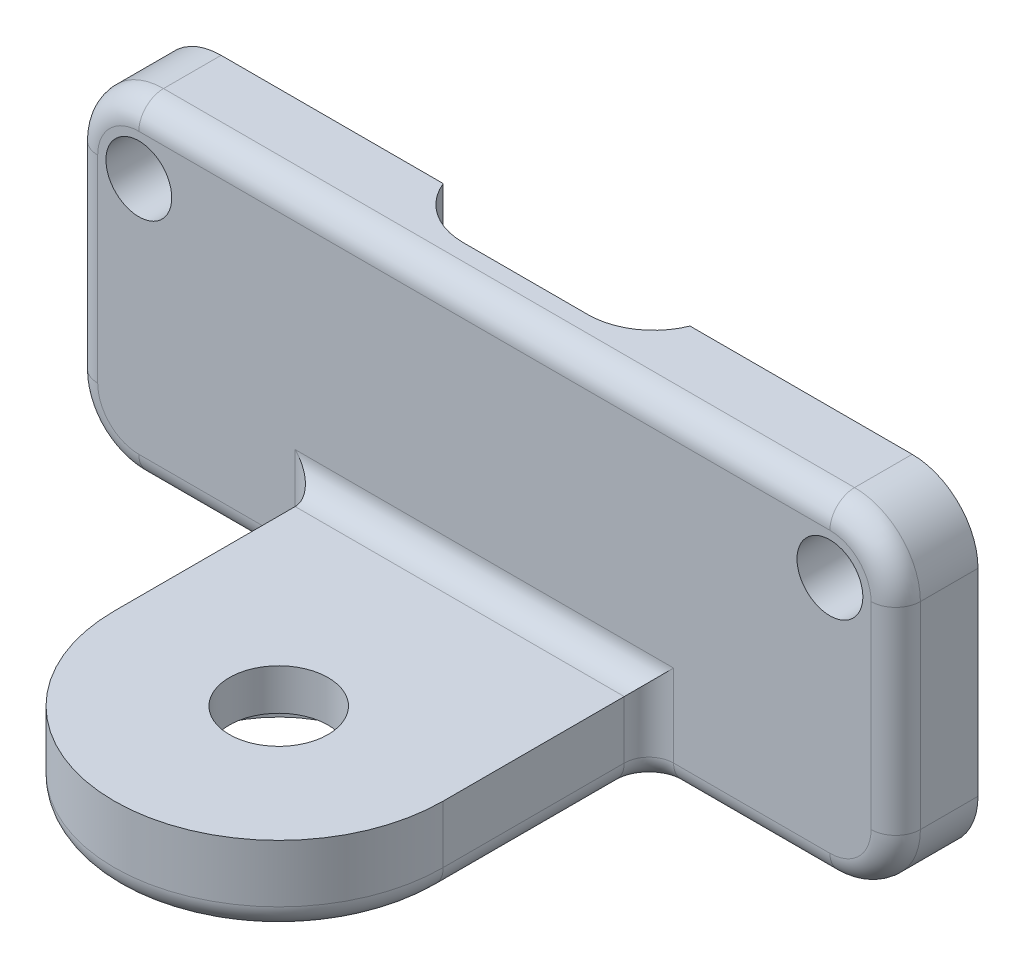
SolidWorks part; units mm, degrees
ref_plane "Спереди" through (0, 0, 0) normal (0, 0, 1) x (1, 0, 0)
ref_plane "Сверху" through (0, 0, 0) normal (0, 1, 0) x (1, 0, 0)
ref_plane "Справа" through (0, 0, 0) normal (1, 0, 0) x (0, 0, -1)
sketch "Эскиз1" plane through (0, 0, 0) normal (0, 0, 1) x (1, 0, 0)
  line L1 (50, -20) -> (-50, -20)
  line L2 (50, -20) -> (50, 20)
  line L3 (50, 20) -> (-50, 20)
  line L4 (-50, -20) -> (-50, 20)
  line L5 (50, -20) -> (-50, 20) construction
  line L6 (50, 20) -> (-50, -20) construction
  point P0 (0, 0)
  dimension "D1" = 100
  dimension "D2" = 40
extrude "Бобышка-Вытянуть1" add sketch "Эскиз1" along normal blind 10
sketch "Эскиз2" plane through (0, -20, 0) normal (0, -1, 0) x (1, 0, 0)
  line L0 (-20, 0) -> (-20, 35)
  line L1 (-50, 0) -> (50, 0) construction
  line L2 (-20, 0) -> (20, 0)
  line L3 (20, 0) -> (20, 35)
  line L4 (-50, 10) -> (-50, 0) construction
  arc A1 (-20, 35) -> (20, 35) centre (0, 35) cw
  point P4 (-19.4704, 35)
  dimension "D2" = 35
  dimension "D1" = 20
  dimension "D3" = 50
extrude "Бобышка-Вытянуть2" add sketch "Эскиз2" against normal blind 10 contours A1 L3 L2 L0
sketch "Эскиз4" plane through (0, -20, 0) normal (0, -1, 0) x (1, 0, 0)
  line L0 (-50, 0) -> (50, 0) construction
  line L1 (-50, 10) -> (-50, 0) construction
  circle A0 centre (0, 35) radius 12.5
  point P4 (0, 0)
  dimension "D1" = 25
  dimension "D3" = 50
  dimension "D2" = 35
extrude "Вырез-Вытянуть1" cut sketch "Эскиз4" against normal blind 5 contours A0
sketch "Эскиз5" plane through (0, -15, 0) normal (0, -1, 0) x (1, 0, 0)
  line L0 (-50, 10) -> (-50, 0) construction
  line L1 (-50, 0) -> (50, 0) construction
  circle A0 centre (0, 35) radius 6
  point P6 (24.3464, 47.591)
  point P9 (-32.7059, 65.9829)
  dimension "D1" = 12
  dimension "D2" = 50
  dimension "D3" = 35
extrude "Вырез-Вытянуть2" cut sketch "Эскиз5" against normal blind 5 contours A0
sketch "Эскиз6" plane through (0, -20, 0) normal (0, -1, 0) x (1, 0, 0)
  line L0 (-50, 0) -> (50, 0) construction
  line L1 (-15, 0) -> (15, 0)
  line L2 (-15, 0) -> (-15, 5)
  line L3 (-15, 5) -> (15, 5)
  line L4 (15, 0) -> (15, 5)
  point P6 (0, 0)
  point P8 (-17.1496, 0)
  dimension "D1" = 30
  dimension "D2" = 5
  dimension "D3" = 35
extrude "Вырез-Вытянуть3" cut sketch "Эскиз6" against normal through all contours L2 L1 L4 L3
fillet "Скругление1" radius 8 6 edges at (50, -20, 5) (-50, -20, 5) (-50, 20, 5) (50, 20, 5) (-15, 0, 5) (15, 0, 5)
fillet "Скругление2" radius 3 15 edges at (20, -20, 22.5) (-20, -20, 22.5) (20, -15, 10) (0, -10, 10) (-20, -15, 10) (-31, -20, 10) (-47.6569, -17.6569, 10) (-50, 0, 10) (-47.6569, 17.6569, 10) (0, 20, 10) (47.6569, 17.6569, 10) (50, 0, 10) (47.6569, -17.6569, 10) (31, -20, 10) (0, -20, 55)
sketch "Эскиз7" plane through (0, 0, 10) normal (0, 0, 1) x (1, 0, 0)
  line L0 (0, 17) -> (0, -17) construction
  line L1 (42, 17) -> (-42, 17) construction
  line L2 (-20, -17) -> (20, -17) construction
  line L3 (-42, 20) -> (42, 20) construction
  circle A0 centre (-42, 12) radius 4
  circle A1 centre (42, 12) radius 4
  point P8 (-42, 9.2139)
  dimension "D1" = 8
  dimension "D2" = 42
  dimension "D3" = 8
extrude "Вырез-Вытянуть5" cut sketch "Эскиз7" against normal through all
